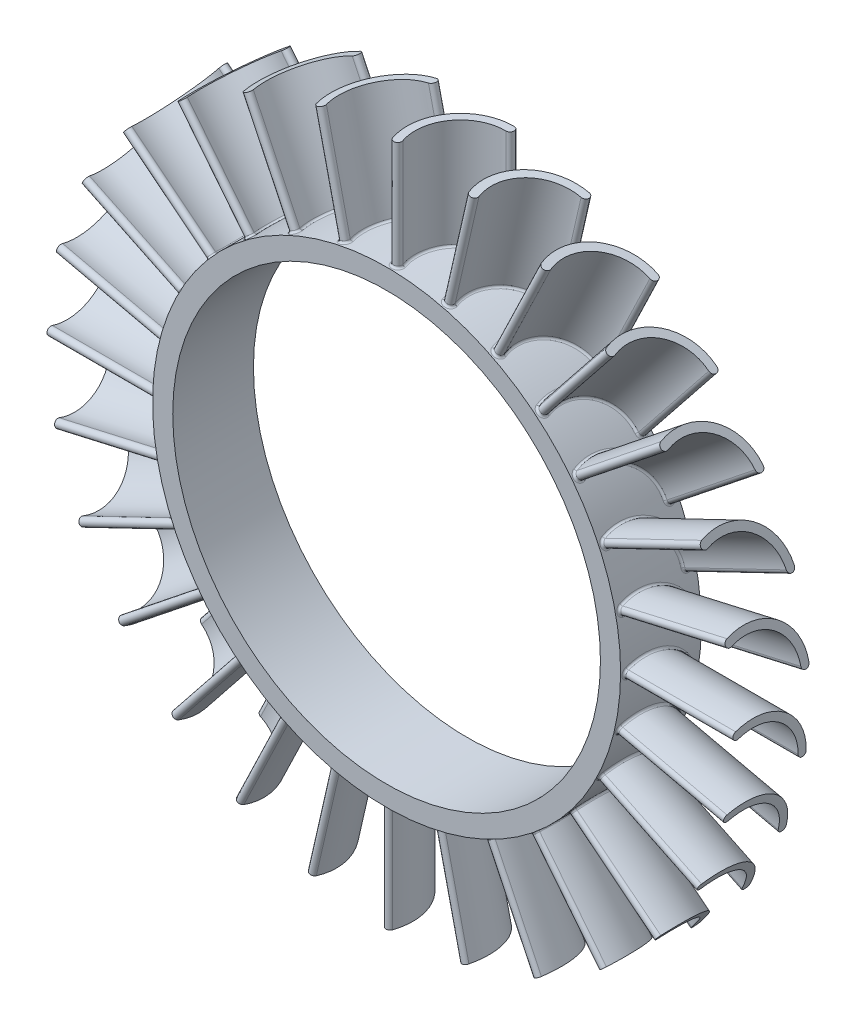
SolidWorks part; units mm, degrees
ref_plane "Front Plane" through (0, 0, 0) normal (0, 0, 1) x (1, 0, 0)
ref_plane "Top Plane" through (0, 0, 0) normal (0, 1, 0) x (1, 0, 0)
ref_plane "Right Plane" through (0, 0, 0) normal (1, 0, 0) x (0, 0, -1)
sketch "Sketch1" plane through (0, 0, 0) normal (0, 0, 1) x (1, 0, 0)
  circle A0 centre (0, 0) radius 53
  circle A1 centre (0, 0) radius 58
  dimension "D1" = 106
  dimension "D2" = 116
extrude "Boss-Extrude1" add sketch "Sketch1" along normal mid plane 20
sketch "Sketch2" plane through (0, 0, 0) normal (0, 1, 0) x (1, 0, 0)
  line L0 (-58, -10) -> (58, -10) construction
  line L1 (53, 10) -> (-53, 10) construction
  arc A0 (0, -8.5) -> (12.6254, 9) centre (12.4796, -4.1991) cw
  arc A1 (1.8909, -7.8483) -> (12.6033, 7.0001) centre (12.4796, -4.1991) cw
  arc A2 (12.6254, 9) -> (12.6033, 7.0001) centre (12.6144, 8.0001) cw
  arc A3 (0, -8.5) -> (1.8909, -7.8483) centre (0.9454, -8.1742) ccw
  dimension "D1" = 1.5
  dimension "D2" = 1
  dimension "D3" = 2
extrude "Boss-Extrude2" add sketch "Sketch2" along normal blind 30 from offset 55
fillet "Fillet1" radius 0.5 4 edges at (1.1752, 57.9881, 9.1474) (1.4741, 57.9813, -3.0891) (11.6343, 56.8212, -8.1987) (2.4777, 57.9471, -0.8408)
pattern_circular "CirPattern1" count 28 over 360 about axis through (0, 0, 10) along (0, 0, -1) of "Fillet1", "Boss-Extrude2"
